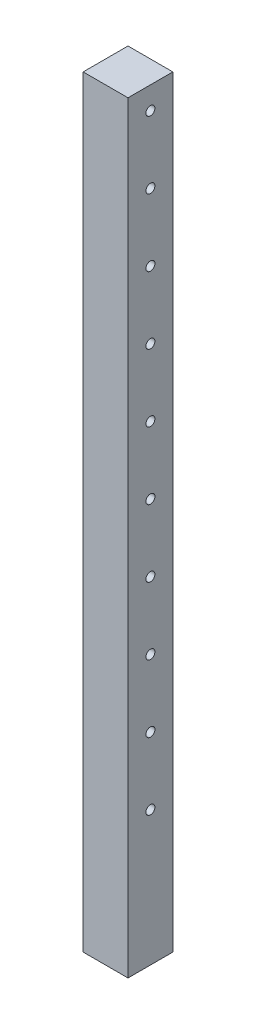
SolidWorks part; units mm, degrees
material "Concreto"
ref_plane "Plano frontal" through (0, 0, 0) normal (0, 0, 1) x (1, 0, 0)
ref_plane "Plano superior" through (0, 0, 0) normal (0, 1, 0) x (1, 0, 0)
ref_plane "Plano direito" through (0, 0, 0) normal (1, 0, 0) x (0, 0, -1)
sketch "Esboço1" plane through (0, 0, 0) normal (0, 1, 0) x (1, 0, 0)
  line L1 (-50, 50) -> (50, 50)
  line L2 (-50, 50) -> (-50, -50)
  line L3 (-50, -50) -> (50, -50)
  line L4 (50, 50) -> (50, -50)
  line L5 (-50, 50) -> (50, -50) construction
  line L6 (-50, -50) -> (50, 50) construction
  point P0 (0, 0)
  dimension "D1" = 100
  dimension "D2" = 100
extrude "Ressalto-extrusão1" add sketch "Esboço1" along normal blind 1700
sketch "Esboço2" plane through (-50, 0, 0) normal (-1, 0, 0) x (0, 0, 1)
  circle A0 centre (0, 1650) radius 10
  circle A1 centre (0, 1500) radius 10
  circle A2 centre (0, 1350) radius 10
  circle A3 centre (0, 1200) radius 10
  circle A4 centre (0, 1050) radius 10
  circle A5 centre (0, 900) radius 10
  circle A6 centre (0, 750) radius 10
  circle A7 centre (0, 600) radius 10
  circle A8 centre (0, 450) radius 10
  circle A9 centre (0, 300) radius 10
  dimension "D1" = 20
  dimension "D2" = 10
extrude "Corte-extrusão1" cut sketch "Esboço2" against normal through all
